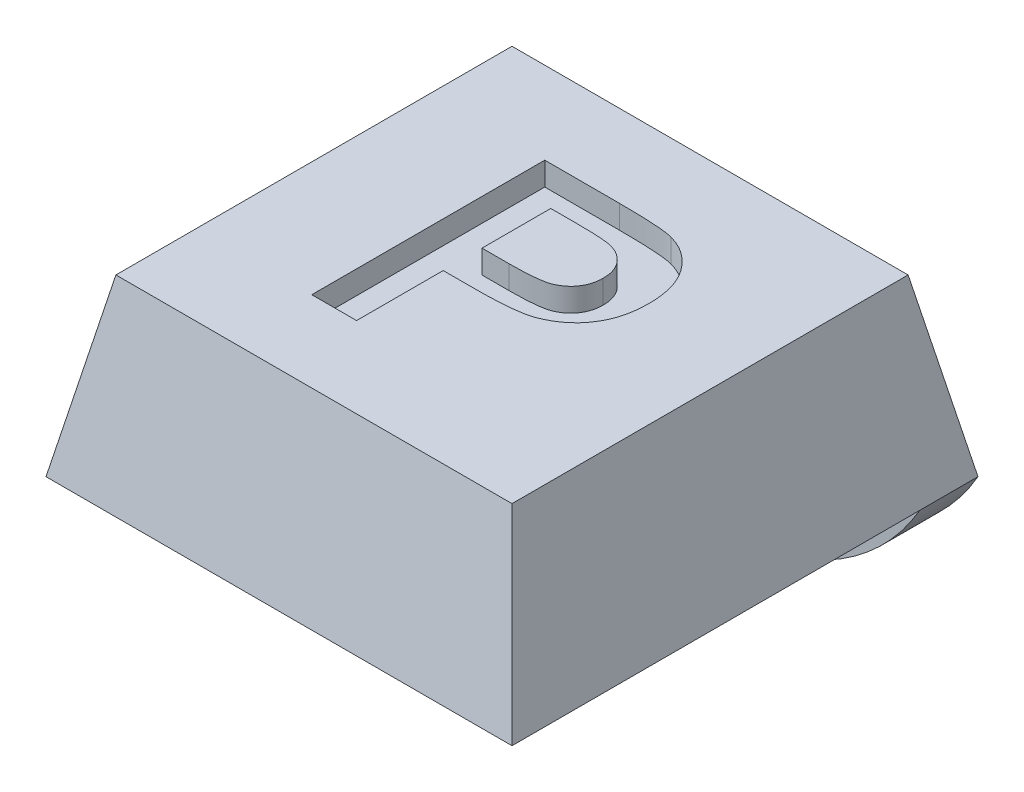
SolidWorks part; units mm, degrees
ref_plane "Front Plane" through (0, 0, 0) normal (0, 0, 1) x (1, 0, 0)
ref_plane "Top Plane" through (0, 0, 0) normal (0, 1, 0) x (1, 0, 0)
ref_plane "Right Plane" through (0, 0, 0) normal (1, 0, 0) x (0, 0, -1)
sketch "Sketch1" plane through (0, 0, 0) normal (0, 1, 0) x (1, 0, 0)
  line L1 (0, 0) -> (8, 0)
  line L2 (0, 0) -> (0, 8)
  line L3 (0, 8) -> (8, 8)
  line L4 (8, 0) -> (8, 8)
  dimension "D1" = 8
  dimension "D2" = 8
extrude "Boss-Extrude1" add sketch "Sketch1" along normal blind 3
sketch "Sketch2" plane through (0, 0, 0) normal (0, 0, 1) x (1, 0, 0)
  line L0 (0, 0) -> (0.6, 3)
  line L1 (0, 3) -> (8, 3) construction
  line L2 (0.6, 3) -> (0, 3)
  line L3 (0, 3) -> (0, 0)
  line L4 (8, 0) -> (7.4, 3)
  line L5 (7.4, 3) -> (8, 3)
  line L6 (8, 3) -> (8, 0)
  dimension "D1" = 0.6
  dimension "D2" = 0.6
extrude "Cut-Extrude1" cut sketch "Sketch2" against normal through all both and the other way through all
sketch "Sketch3" plane through (0, 0, 0) normal (1, 0, 0) x (0, 0, -1)
  line L0 (0, 0) -> (0.6, 3)
  line L1 (8, 3) -> (0, 3) construction
  line L2 (0.6, 3) -> (0, 3)
  line L3 (0, 3) -> (0, 0)
  line L4 (8, 3) -> (7.4, 3)
  line L5 (7.4, 3) -> (8, 0)
  line L6 (8, 3) -> (8, 0)
  dimension "D1" = 0.6
  dimension "D2" = 0.6
extrude "Cut-Extrude2" cut sketch "Sketch3" along normal blind 11
sketch "Sketch4" plane through (0, 0, 0) normal (0, -1, 0) x (1, 0, 0)
  line L0 (8, 0) -> (8, -8) construction
  line L3 (0, 0) -> (8, 0) construction
  circle A0 centre (4, -3.75) radius 1.8
  dimension "D1" = 3.6
  dimension "D2" = 4
  dimension "D3" = 3.75
extrude "Cut-Extrude3" cut sketch "Sketch4" against normal blind 0.8
sketch "Sketch5" plane through (0, 0, 0) normal (0, -1, 0) x (1, 0, 0)
  line L0 (8, 0) -> (8, -8) construction
  line L1 (0, -8) -> (8, -8)
  line L2 (0, -8) -> (0, -7)
  line L3 (0, -7) -> (8, -7)
  line L4 (8, -8) -> (8, -7)
  dimension "D1" = 1
extrude "Boss-Extrude2" add sketch "Sketch5" along normal blind 2
fillet "Fillet1" radius 4 2 edges at (8, -2, -7.5) (0, -2, -7.5)
sketch "Sketch6" plane through (0, 3, 0) normal (0, 1, 0) x (1, 0, 0)
  text T0 "P" font "Arial" height 4
extrude "Cut-Extrude4" cut sketch "Sketch6" against normal blind 0.4
